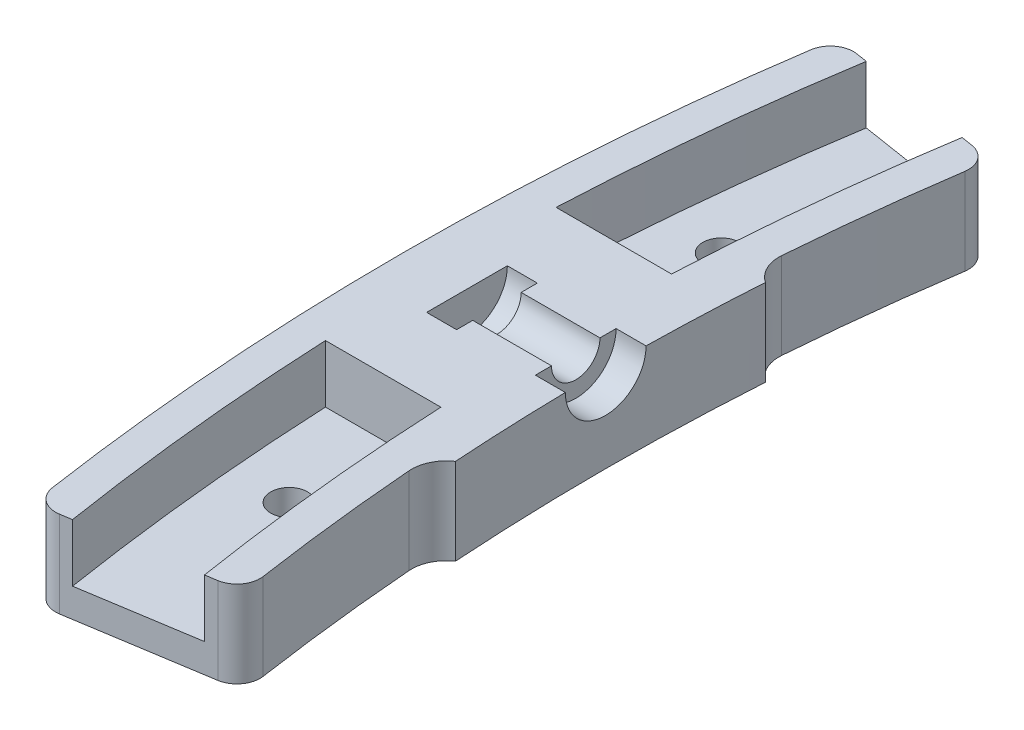
SolidWorks part; units mm, degrees
ref_plane "Front Plane" through (0, 0, 0) normal (0, 0, 1) x (1, 0, 0)
ref_plane "Top Plane" through (0, 0, 0) normal (0, 1, 0) x (1, 0, 0)
ref_plane "Right Plane" through (0, 0, 0) normal (1, 0, 0) x (0, 0, -1)
sketch "Sketch1" plane through (0, 0, 0) normal (0, 1, 0) x (1, 0, 0)
  line L0 (0, 0) -> (-217.2914, -34.4156) construction
  line L1 (0, 0) -> (-217.2914, 34.4156) construction
  line L2 (0, 0) -> (-215, 0) construction
  line L3 (-217.2914, 34.4156) -> (-207.4146, 32.8512)
  line L4 (-207.4146, -32.8512) -> (-217.2914, -34.4156)
  line L5 (0, 0) -> (-220.2545, -34.8849) construction
  line L6 (0, 0) -> (-220.2545, 34.8849) construction
  line L7 (-220.2545, 34.8849) -> (-204.4515, 32.3819)
  line L8 (-220.2545, -34.8849) -> (-204.4515, -32.3819)
  arc A0 (-217.2914, 34.4156) -> (-217.2914, -34.4156) centre (0, 0) ccw
  arc A1 (-207.4146, 32.8512) -> (-207.4146, -32.8512) centre (0, 0) ccw
  arc A2 (-212.353, -33.6334) -> (-212.353, 33.6334) centre (0, 0) cw construction
  arc A4 (-204.4515, 32.3819) -> (-204.4515, -32.3819) centre (0, 0) ccw
  arc A5 (-220.2545, 34.8849) -> (-220.2545, -34.8849) centre (0, 0) ccw
  dimension "D1" = 220
  dimension "D2" = 210
  dimension "D3" = 5
  dimension "D5" = 3
  dimension "D6" = 3
  dimension "D4" = 18
extrude "Boss-Extrude1" add sketch "Sketch1" along normal blind 10 contours A1 L3 A0 L4 | L7 A5 L8 A0 | A4 L7 A1 L8 region at (-220.5936, 0, 0) region at (-214.1555, 0, 0) region at (-207.6472, 0, 0)
ref_plane "Plane1" through (-215, 0, 0) normal (1, 0, 0) x (0, 0, -1)
sketch "Sketch15" plane through (0, 10, 0) normal (0, 1, 0) x (1, 0, 0)
  line L0 (-207.4146, -32.8512) -> (-217.2914, -34.4156) construction
  line L1 (-205, 10) -> (-225, 10)
  line L2 (-205, 10) -> (-205, -10)
  line L3 (-205, -10) -> (-225, -10)
  line L4 (-225, 10) -> (-225, -10)
  line L5 (-205, 10) -> (-225, -10) construction
  line L6 (-205, -10) -> (-225, 10) construction
  line L7 (-217.2914, 34.4156) -> (-207.4146, 32.8512) construction
  line L8 (-207.4146, -32.8512) -> (-217.2914, -34.4156)
  line L9 (-217.2914, 34.4156) -> (-207.4146, 32.8512)
  arc A2 (-207.4146, 32.8512) -> (-207.4146, -32.8512) centre (0, 0) ccw construction
  arc A3 (-217.2914, 34.4156) -> (-217.2914, -34.4156) centre (0, 0) ccw construction
  arc A4 (-207.4146, 32.8512) -> (-207.4146, -32.8512) centre (0, 0) ccw
  arc A5 (-217.2914, 34.4156) -> (-217.2914, -34.4156) centre (0, 0) ccw
  point P0 (-215, 0)
  line M5 (-220.2545, -34.8849) -> (-204.4515, -32.3819)
  line M7 (-204.4515, 32.3819) -> (-220.2545, 34.8849)
  dimension "D1" = 20
  dimension "D2" = 20
extrude "Cut-Extrude1" cut sketch "Sketch15" against normal blind 5 contours A5 L1 A4 M7 | L3 A5 A4 M5 region at (-213.8328, 10, -21.8433) region at (-213.8328, 10, 21.8433)
ref_plane "Plane2" through (-215, 0, 0) normal (-1, 0, 0) x (0, 0, 1)
sketch "Sketch12" plane through (0, 0, 0) normal (0, 1, 0) x (1, 0, 0)
  line L0 (0, 0) -> (-214.1819, -18.7385) construction
  line L1 (0, 0) -> (-213.1606, -28.0631) construction
  line L2 (0, 0) -> (-215, 0) construction
  line L3 (0, 0) -> (-215, 0) construction
  line L4 (0, 0) -> (-214.1819, 18.7385) construction
  line L5 (0, 0) -> (-213.1606, 28.0631) construction
  arc A0 (-212.353, 33.6334) -> (-212.353, -33.6334) centre (0, 0) ccw construction
  dimension "D1" = 10
  dimension "D2" = 15
hole_wizard "Ø3.2 (3.2) Diameter Hole1" positions "Sketch18" profile "Sketch17" hole size "Ø3.2" standard "ISO" end condition through all
sketch "Sketch18" plane through (0, 0, 0) normal (0, -1, 0) x (-1, 0, 0)
  point P3 (214.1819, -18.7385)
  point P6 (214.1819, 18.7385)
sketch "Sketch17" plane through (-214.1819, 0, 18.7385) normal (1, 0, 0) x (0, 0, -1)
  line L0 (0, 0) -> (0, 10)
  line L1 (0, 10) -> (1.6, 10)
  line L2 (1.6, 10) -> (1.6, 0)
  line L5 (1.6, 0) -> (0, 0)
  line L11 (0, -6.35) -> (0, 107.95) construction
  dimension "Thru Hole Dia." = 3.2
  dimension "Thru Hole Depth" = 10
sketch "Sketch19" plane through (0, 0, 0) normal (0, 1, 0) x (1, 0, 0)
  line L0 (0, 0) -> (-205.06, -13.4403) construction
  line L1 (0, 0) -> (-205.5, 0) construction
  line L2 (-205.06, -13.4403) -> (-206.5568, -13.5384)
  line L3 (-205.06, 13.4403) -> (-206.5568, 13.5384)
  arc A0 (-205.06, 13.4403) -> (-205.06, -13.4403) centre (0, 0) ccw
  arc A1 (-204.4515, 32.3819) -> (-204.4515, -32.3819) centre (0, 0) ccw construction
  arc A2 (-206.5568, 13.5384) -> (-206.5568, -13.5384) centre (0, 0) ccw
  dimension "D1" = 205.5
  dimension "D2" = 3.75
extrude "Boss-Extrude2" add sketch "Sketch19" along normal blind 10
fillet "Fillet1" radius 3 2 edges at (-206.5568, 5, -13.5384) (-206.5568, 5, 13.5384)
fillet "Fillet2" radius 2 4 edges at (-220.2545, 5, -34.8849) (-220.2545, 5, 34.8849) (-204.4515, 5, 32.3819) (-204.4515, 5, -32.3819)
sketch "Sketch20" plane through (0, 10, 0) normal (0, 1, 0) x (1, 0, 0)
  line L0 (0, 0) -> (-185, 0) construction
  line L1 (-185, 0) -> (-197.5, 0) construction
  dimension "D1" = 185
  dimension "D2" = 12.5
ref_plane "Plane3" through (-197.5, 0, 0) normal (1, 0, 0) x (0, 0, -1)
sketch "Sketch26" plane through (0, 0, 0) normal (0, -1, 0) x (1, 0, 0)
  line L2 (-218.2702, -34.5706) -> (-206.4174, -32.6933)
  line L3 (-206.4174, 32.6933) -> (-218.2702, 34.5706)
  line L4 (-218.2702, -34.5706) -> (-206.4174, -32.6933)
  line L5 (-206.4174, 32.6933) -> (-218.2702, 34.5706)
  arc A10 (-220.5612, 32.8902) -> (-220.5612, -32.8902) centre (0, 0) ccw
  arc A11 (-220.5612, -32.8902) -> (-218.2702, -34.5706) centre (-218.5831, -32.5952) ccw
  arc A12 (-206.4174, -32.6933) -> (-204.752, -30.424) centre (-206.7303, -30.7179) ccw
  arc A13 (-206.3684, -16.1583) -> (-204.752, -30.424) centre (0, 0) ccw
  arc A14 (-205.06, -13.4403) -> (-206.3684, -16.1583) centre (-203.3775, -15.9241) ccw
  arc A15 (-205.06, 13.4403) -> (-205.06, -13.4403) centre (0, 0) ccw
  arc A16 (-206.3684, 16.1583) -> (-205.06, 13.4403) centre (-203.3775, 15.9241) ccw
  arc A17 (-204.752, 30.424) -> (-206.3684, 16.1583) centre (0, 0) ccw
  arc A18 (-204.752, 30.424) -> (-206.4174, 32.6933) centre (-206.7303, 30.7179) ccw
  arc A19 (-218.2702, 34.5706) -> (-220.5612, 32.8902) centre (-218.5831, 32.5952) ccw
  arc A20 (-220.5612, 32.8902) -> (-220.5612, -32.8902) centre (0, 0) ccw
  arc A21 (-220.5612, -32.8902) -> (-218.2702, -34.5706) centre (-218.5831, -32.5952) ccw
  arc A22 (-206.4174, -32.6933) -> (-204.752, -30.424) centre (-206.7303, -30.7179) ccw
  arc A23 (-206.3684, -16.1583) -> (-204.752, -30.424) centre (0, 0) ccw
  arc A24 (-205.06, -13.4403) -> (-206.3684, -16.1583) centre (-203.3775, -15.9241) ccw
  arc A25 (-205.06, 13.4403) -> (-205.06, -13.4403) centre (0, 0) ccw
  arc A26 (-206.3684, 16.1583) -> (-205.06, 13.4403) centre (-203.3775, 15.9241) ccw
  arc A27 (-204.752, 30.424) -> (-206.3684, 16.1583) centre (0, 0) ccw
  arc A28 (-204.752, 30.424) -> (-206.4174, 32.6933) centre (-206.7303, 30.7179) ccw
  arc A29 (-218.2702, 34.5706) -> (-220.5612, 32.8902) centre (-218.5831, 32.5952) ccw
  dimension "D1" = 0
extrude "Cut-Extrude6" cut sketch "Sketch26" against normal blind 2.5
sketch "Sketch27" plane through (0, 0, 0) normal (0, 1, 0) x (1, 0, 0)
  line L0 (0, 0) -> (-205, 0) construction
  line L1 (0, 0) -> (-215, 0) construction
  line L2 (-205, 0) -> (-217.5, 0) construction
  arc A0 (-205.06, 13.4403) -> (-205.06, -13.4403) centre (0, 0) ccw construction
  point P5 (-205.5, 0)
  dimension "D1" = 205
  dimension "D2" = 12.5
ref_plane "Plane4" through (-217.5, 0, 0) normal (1, 0, 0) x (0, 0, -1)
sketch "Sketch28" plane through (-217.5, 0, 0) normal (1, 0, 0) x (0, 0, -1)
  line L0 (13.4403, 10) -> (-13.4403, 10) construction
  circle A0 centre (0, 10) radius 3.5
  dimension "D1" = 7
extrude "Cut-Extrude7" cut sketch "Sketch28" along normal blind 2.6
sketch "Sketch29" plane through (0, 10, 0) normal (0, 1, 0) x (1, 0, 0)
  line L0 (-205, 0) -> (-217.5, 0) construction
  line L1 (-208.0702, 0) -> (-205.4702, 0)
  line L2 (-208.0702, 0) -> (-208.0702, -3.5)
  line L3 (-208.0702, -3.5) -> (-205.4702, -3.5)
  line L4 (-205.4702, 0) -> (-205.4702, -3.5)
  line L6 (-217.5, 0) -> (-205, 0) construction
  arc A0 (-205.06, 13.4403) -> (-205.06, -13.4403) centre (0, 0) ccw construction
  dimension "D1" = 2.6
  dimension "D2" = 7
revolve "Cut-Revolve1" cut sketch "Sketch29" angle 360 about L6
sketch "Sketch30" plane through (-208.0702, 0, 0) normal (1, 0, 0) x (0, 0, -1)
  line L0 (3.5, 10) -> (-3.5, 10) construction
  circle A0 centre (0, 10) radius 2.1
  dimension "D1" = 4.2
extrude "Cut-Extrude8" cut sketch "Sketch30" against normal up to surface (6.8298 mm away) up to face at (-214.9, 8.25, 0)
